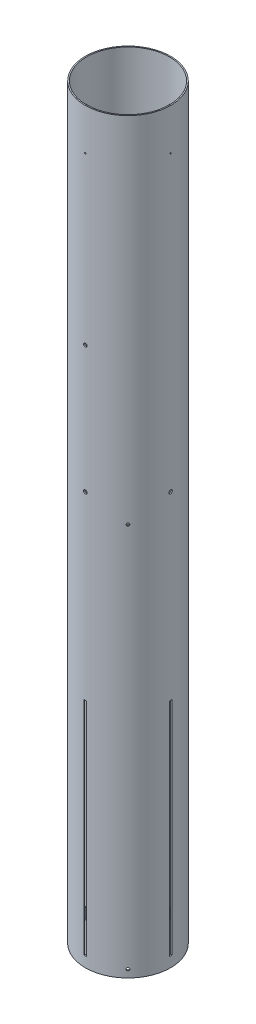
SolidWorks part; units mm, degrees
material "E-Glass Fiber"
ref_plane "Front Plane" through (0, 0, 0) normal (0, 0, 1) x (1, 0, 0)
ref_plane "Top Plane" through (0, 0, 0) normal (0, 1, 0) x (1, 0, 0)
ref_plane "Right Plane" through (0, 0, 0) normal (1, 0, 0) x (0, 0, -1)
sketch "Sustainer Tube Profile" plane through (0, 0, 0) normal (0, 1, 0) x (1, 0, 0)
  circle A0 centre (0, 0) radius 76.2
  circle A1 centre (0, 0) radius 78.359
  dimension "D2" = 156.718
extrude "Sustainer Tube Body" add sketch "Sustainer Tube Profile" along normal blind 1371.6
ref_plane "Plane1" through (0, 0, 78.359) normal (0, 0, 1) x (1, 0, 0)
sketch "Fin Slot Profile" plane through (0, 0, 78.359) normal (0, 0, 1) x (1, 0, 0)
  line L0 (0, 0) -> (0, 1371.6) construction
  line L5 (76.2, 1371.6) -> (-76.2, 1371.6) construction
  line L6 (-78.359, 0) -> (78.359, 0) construction
  line L7 (2.3813, 19.05) -> (-2.3813, 19.05)
  line L8 (0, 19.05) -> (0, 425.45)
  line L9 (2.3813, 425.45) -> (-2.3813, 425.45)
  line L10 (-2.3813, 19.05) -> (-2.3813, 425.45)
  line L11 (2.3813, 19.05) -> (2.3813, 425.45)
  dimension "D1" = 406.4
  dimension "D2" = 19.05
  dimension "D3" = 2.3813
extrude "Fin Slot Cut" cut sketch "Fin Slot Profile" against normal up to surface (2.1962 mm away) contours L7 L11 L9 L8 | L10 L7 L8 L9 region at (1.1906, 222.25, 78.359) region at (-1.1906, 222.25, 78.359) up to face at (0, 1371.6, 76.2)
pattern_circular "Fin Slot Pattern" count 4 over 360 about axis through (0, 1371.6, 0) along (0, 1, 0) of "Fin Slot Cut"
sketch "Sketch1" plane through (0, 0, 0) normal (0, 0, 1) x (1, 0, 0)
  line L0 (76.2, 1371.6) -> (-76.2, 1371.6) construction
  circle A0 centre (0, 1295.4) radius 1.143
  point P2 (0, 0)
  dimension "D1" = 2.286
  dimension "D2" = 76.2
extrude "Cut-Extrude1" cut sketch "Sketch1" against normal through all both and the other way through all
pattern_circular "CirPattern1" count 4 over 360 about axis through (0, 1371.6, 0) along (0, 1, 0) of "Cut-Extrude1"
sketch "Sketch2" plane through (0, 0, 0) normal (0, 0, 1) x (1, 0, 0)
  line L0 (76.2, 1371.6) -> (-76.2, 1371.6) construction
  circle A0 centre (0, 990.6) radius 3.175
  point P2 (0, 0)
  point P4 (0, 0)
  dimension "D1" = 6.35
  dimension "D2" = 381
extrude "Cut-Extrude2" cut sketch "Sketch2" against normal through all both and the other way through all
sketch "Sketch3" plane through (0, 0, 0) normal (0, 0, 1) x (1, 0, 0)
  line L0 (78.359, 1371.6) -> (-78.359, 1371.6) construction
  circle A0 centre (0, 756.9962) radius 3.175
  point P2 (0, 0)
  dimension "D2" = 6.35
  dimension "D1" = 614.6038
extrude "Cut-Extrude3" cut sketch "Sketch3" against normal through all both and the other way through all
pattern_circular "CirPattern2" count 4 over 360 about axis through (0, 1371.6, 0) along (0, 1, 0) of "Cut-Extrude3"
ref_plane "Plane2" through (55.4082, 0, 55.4082) normal (0.7071, 0, 0.7071) x (0, -1, 0)
sketch "Sketch4" plane through (55.4082, 0, 55.4082) normal (0.7071, 0, 0.7071) x (0, -1, 0)
  circle A0 centre (-14.0462, 0) radius 2.5019
  circle A1 centre (-721.2584, 0) radius 2.5019
  point P4 (0, 0)
  dimension "D2" = 14.0462
  dimension "D3" = 721.2584
extrude "Cut-Extrude4" cut sketch "Sketch4" against normal up to surface and the other way through all up to face at (-76.1373, 756.269, 3.0906)
equation "\"Length\"= 54"
equation "\"Outer Diameter\"= 6.17"
equation "\"Inner Diameter\"= 6"
equation "\"Wall Thickness\"= 0.085"
equation "\"D1@Sustainer Tube Profile\" = \"Inner Diameter\""
equation "\"D2@Sustainer Tube Profile\" = \"Outer Diameter\""
equation "\"D1@Sustainer Tube Body\" = \"Length\""
equation "\"Root Chord\"= 16"
equation "\"Fin Offset\"= 3 / 4"
equation "\"D1@Fin Slot Profile\"=\"Root Chord\" "
equation "\"D2@Fin Slot Profile\" = \"Fin Offset\""
equation "\"Fin Thickness\"= ( 3 / 16 ) / 2"
equation "\"D3@Fin Slot Profile\"=\"Fin Thickness\""
equation "\"Shear Pin Dia\"= 3 / 32"
equation "\"Shear Pin Offset\"= 3"
equation "\"Bulkhead Screw Dia\"= 1 / 4"
equation "\"Bulkhead Screw Offset\"= 24.197"
equation "\"Rail Button Dia\"= 0.197"
equation "\"Rail Button Aft Offset\"= 0.553"
equation "\"Rail Button Forward Offset\"= 28.396"
equation "\"Vent Hole Dia\"= 1 / 4"
equation "\"Vent Hole Offset\"= 15"
equation "\"D1@Sketch2\"=\"Vent Hole Dia\""
equation "\"D2@Sketch2\"=\"Vent Hole Offset\""
equation "\"D1@Sketch3\"=\"Bulkhead Screw Offset\""
equation "\"D2@Sketch3\"=\"Bulkhead Screw Dia\""
equation "\"D1@Sketch4\"=\"Rail Button Dia\""
equation "\"D2@Sketch4\"=\"Rail Button Aft Offset\""
equation "\"D3@Sketch4\"=\"Rail Button Forward Offset\""
